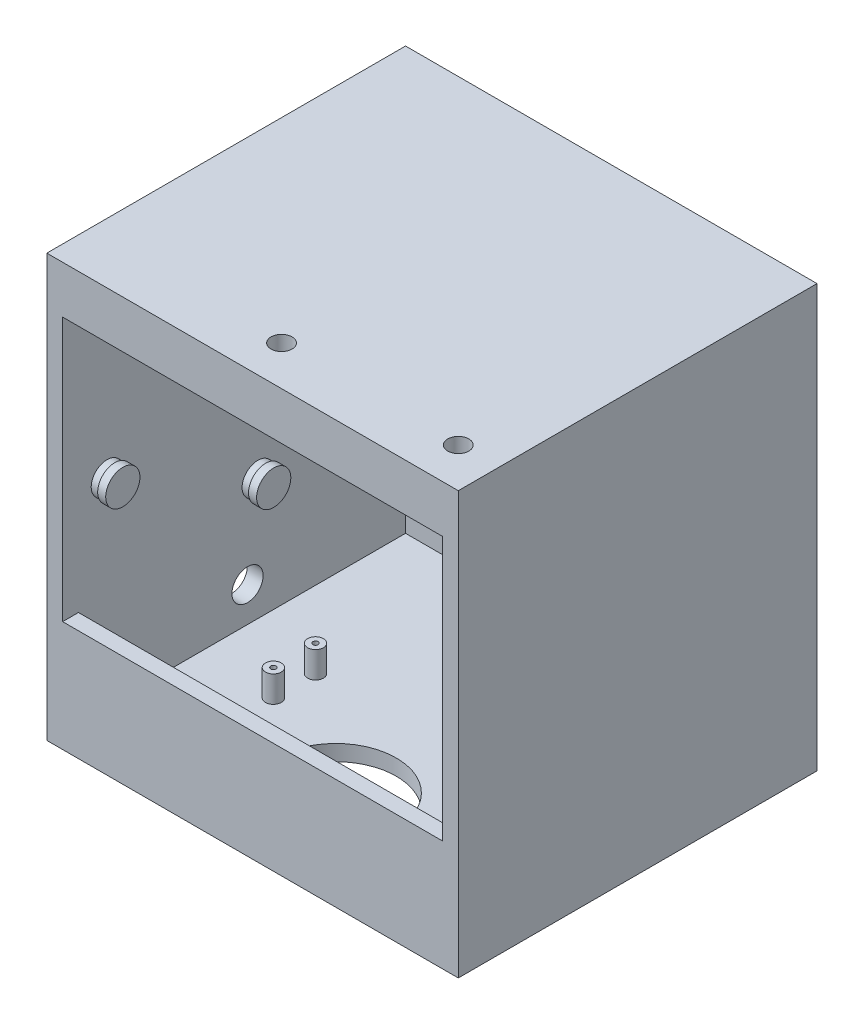
SolidWorks part; units mm, degrees
ref_plane "Front Plane" through (0, 0, 0) normal (0, 0, 1) x (1, 0, 0)
ref_plane "Top Plane" through (0, 0, 0) normal (0, 1, 0) x (1, 0, 0)
ref_plane "Right Plane" through (0, 0, 0) normal (1, 0, 0) x (0, 0, -1)
sketch "Base Plate Sketch" plane through (0, 0, 0) normal (0, 1, 0) x (1, 0, 0)
  line L1 (-176.9042, 232.645) -> (280.2958, 232.645)
  line L2 (-176.9042, 232.645) -> (-176.9042, -161.055)
  line L3 (-176.9042, -161.055) -> (280.2958, -161.055)
  line L4 (280.2958, 232.645) -> (280.2958, -161.055)
  line L5 (-195.9542, 251.695) -> (299.3458, 251.695)
  line L6 (-195.9542, 251.695) -> (-195.9542, -180.105)
  line L7 (-195.9542, -180.105) -> (299.3458, -180.105)
  line L8 (299.3458, 251.695) -> (299.3458, -180.105)
  line L9 (51.6958, 232.645) -> (51.6958, -161.055)
  circle A0 centre (51.6958, -80.0925) radius 73.025
  circle A1 centre (-72.1292, -82.0299) radius 4.1
  circle A2 centre (-72.1292, 203.67) radius 4.7625
  circle A3 centre (-84.8292, 32.22) radius 9.5
  circle A4 centre (-84.8292, -18.5299) radius 9.5
  circle A5 centre (-84.8292, 32.22) radius 3.175
  circle A6 centre (-84.8292, -18.5299) radius 3.175
  circle A7 centre (175.5208, -82.0299) radius 4.1
  circle A8 centre (188.2208, -18.5299) radius 3.175
  circle A9 centre (188.2208, -18.5299) radius 9.5
  circle A10 centre (188.2208, 32.22) radius 3.175
  circle A11 centre (188.2208, 32.22) radius 9.5
  circle A12 centre (175.5208, 203.67) radius 4.7625
  dimension "D7" = 146.05
  dimension "D9" = 8.2
  dimension "D10" = 12.7
  dimension "D11" = 63.5
  dimension "D12" = 9.525
  dimension "D13" = 12.7
  dimension "D14" = 19
  dimension "D15" = 19
  dimension "D19" = 6.35
  dimension "D20" = 6.35
  dimension "D1" = 393.7
  dimension "D2" = 457.2
  dimension "D3" = 19.05
  dimension "D4" = 19.05
  dimension "D5" = 19.05
  dimension "D6" = 19.05
  dimension "D8" = 312.7375
  dimension "D16" = 50.75
  dimension "D17" = 123.825
  dimension "D21" = 28.975
  dimension "D22" = 171.45
extrude "Boss-Extrude2" add sketch "Base Plate Sketch" along normal blind 31.75 contours A10 | A11 | A8 | A9 | A5 | A3 | A6 | A4
extrude "Boss-Extrude3" add sketch "Sketch1<5>" against normal blind 19.05 contours L5 L8 L7 L6
sketch "Sketch1<5>" plane through (0, 0, 0) normal (0, 1, 0) x (1, 0, 0) same geometry as "Base Plate Sketch"
extrude "Cut-Extrude1" cut sketch "Sketch1<6>" against normal blind 99.05 contours A2 | A1 | A0 | A7 | A12
sketch "Sketch1<6>" plane through (0, 0, 0) normal (0, 1, 0) x (1, 0, 0) same geometry as "Base Plate Sketch"
extrude "Boss-Extrude4" add sketch "Sketch1<7>" along normal blind 469.9 contours L6 L7 L8 L5 | L2 L3 L4 L1
sketch "Sketch1<7>" plane through (0, 0, 0) normal (0, 1, 0) x (1, 0, 0) same geometry as "Base Plate Sketch"
ref_plane "Plane1" through (-176.9042, 0, -232.645) normal (1, 0, 0) x (0, 0, -1)
sketch "Back Wall Sketch" plane through (0, 0, -232.645) normal (0, 0, 1) x (1, 0, 0)
  line L0 (-176.9042, 114.3) -> (280.2958, 114.3)
  line L1 (-176.9042, 469.9) -> (-176.9042, 0) construction
  line L2 (280.2958, 469.9) -> (280.2958, 0) construction
  line L3 (-176.9042, 266.7) -> (280.2958, 266.7)
  line L4 (-176.9042, 0) -> (280.2958, 0) construction
  line L5 (-176.9042, 469.9) -> (280.2958, 469.9) construction
  line L6 (51.6958, 266.7) -> (51.6958, 469.9)
  line L7 (280.2958, 266.7) -> (280.2958, 114.3)
  line L8 (-176.9042, 266.7) -> (-176.9042, 114.3)
  circle A0 centre (-117.9716, 342.325) radius 1.875
  circle A2 centre (-21.0417, 294.9875) radius 1.875
  circle A4 centre (-117.9716, 316.575) radius 1.875
  circle A5 centre (124.4333, 294.9875) radius 1.875
  circle A6 centre (221.3633, 342.325) radius 1.875
  circle A7 centre (221.3633, 316.575) radius 1.875
  circle A8 centre (184.1213, 148.3) radius 16.8
  dimension "D3" = 3.75
  dimension "D4" = 3.75
  dimension "D5" = 3.75
  dimension "D10" = 33.6
  dimension "D1" = 114.3
  dimension "D2" = 152.4
  dimension "D6" = 127.575
  dimension "D7" = 25.75
  dimension "D8" = 174.9125
  dimension "D9" = 155.8625
  dimension "D11" = 96.1746
  dimension "D12" = 118.4
extrude "Boss-Extrude5" add sketch "Back Wall Sketch" against normal blind 38.3 contours L8 L0 L7 L3
extrude "Cut-Extrude2" cut sketch "Back Wall Sketch<5>" against normal blind 19.25 contours L3 L7 L0 L8
sketch "Back Wall Sketch<5>" plane through (0, 0, -232.645) normal (0, 0, 1) x (1, 0, 0) same geometry as "Back Wall Sketch"
extrude "Cut-Extrude5" cut sketch "Back Wall Sketch<7>" against normal blind 28.875 contours A8
sketch "Back Wall Sketch<7>" plane through (0, 0, -232.645) normal (0, 0, 1) x (1, 0, 0) same geometry as "Back Wall Sketch"
extrude "Cut-Extrude6" cut sketch "Back Wall Sketch<8>" against normal blind 28.875 contours A2 | A4 | A0 | A6 | A7 | A5
sketch "Back Wall Sketch<8>" plane through (0, 0, -232.645) normal (0, 0, 1) x (1, 0, 0) same geometry as "Back Wall Sketch"
sketch "Left Wall Sketch" plane through (-176.9042, 0, 0) normal (1, 0, 0) x (0, 0, -1)
  line L0 (232.645, 0) -> (-161.055, 0) construction
  line L1 (251.695, 266.7) -> (251.695, 114.3) construction
  line L2 (232.645, 114.3) -> (232.645, 0) construction
  circle A0 centre (-126.7142, 237.44) radius 19
  circle A1 centre (54.8951, 146) radius 19
  circle A2 centre (42.445, 41.61) radius 18.75
  dimension "D1" = 38
  dimension "D2" = 38
  dimension "D3" = 37.5
  dimension "D5" = 146
  dimension "D9" = 41.61
  dimension "D4" = 237.44
  dimension "D6" = 378.4092
  dimension "D7" = 196.8
  dimension "D8" = 190.2
extrude "Cut-Extrude7" cut sketch "Left Wall Sketch" against normal blind 28.875 contours A2
extrude "Boss-Extrude6" add sketch "Left Wall Sketch<3>" along normal blind 9.35 contours A1 | A0
sketch "Left Wall Sketch<3>" plane through (-176.9042, 0, 0) normal (1, 0, 0) x (0, 0, -1) same geometry as "Left Wall Sketch"
sketch "Sketch5" plane through (-167.5542, 0, 0) normal (1, 0, 0) x (0, 0, -1)
  circle A0 centre (-126.7142, 237.44) radius 20.6
  circle A1 centre (54.8951, 146) radius 20.6
  dimension "D1" = 41.2
  dimension "D2" = 41.2
extrude "Boss-Extrude7" add sketch "Sketch5" along normal blind 9.7
sketch "Chamber Door Sketch" plane through (0, 0, 161.055) normal (0, 0, -1) x (-1, 0, 0)
  line L0 (-280.2958, 431.8) -> (176.9042, 431.8)
  line L1 (-280.2958, 469.9) -> (-280.2958, 0) construction
  line L2 (176.9042, 469.9) -> (176.9042, 0) construction
  line L3 (-280.2958, 114.3) -> (176.9042, 114.3)
  line L4 (176.9042, 0) -> (-280.2958, 0) construction
  line L5 (176.9042, 469.9) -> (-280.2958, 469.9) construction
  line L6 (-280.2958, 431.8) -> (-280.2958, 114.3)
  line L7 (176.9042, 431.8) -> (176.9042, 114.3)
  dimension "D1" = 114.3
  dimension "D2" = 38.1
extrude "Cut-Extrude8" cut sketch "Chamber Door Sketch" against normal blind 25.4 contours L0 L7 L3 L6
sketch "Top Sketch" plane through (0, 469.9, 0) normal (0, 1, 0) x (1, 0, 0)
  line L1 (-195.9542, 251.695) -> (299.3458, 251.695)
  line L2 (-195.9542, 251.695) -> (-195.9542, -180.105)
  line L3 (-195.9542, -180.105) -> (299.3458, -180.105)
  line L4 (299.3458, 251.695) -> (299.3458, -180.105)
extrude "Boss-Extrude8" add sketch "Top Sketch" along normal blind 19.05 contours L4 L3 L2 L1
sketch "Sketch7" plane through (0, 469.9, 0) normal (0, -1, 0) x (1, 0, 0)
  line L0 (-176.9042, -232.645) -> (280.2958, -232.645) construction
  line L1 (22.0201, -181.825) -> (11.0101, -162.755)
  line L2 (11.0101, -162.755) -> (-11.0101, -162.755)
  line L3 (-11.0101, -162.755) -> (-22.0201, -181.825)
  line L4 (-22.0201, -181.825) -> (-11.0101, -200.895)
  line L5 (-11.0101, -200.895) -> (11.0101, -200.895)
  line L6 (11.0101, -200.895) -> (22.0201, -181.825)
  circle A0 centre (0, -181.825) radius 19.07 construction
  point P1 (0, -200.895)
  dimension "D1" = 38.14
  dimension "D2" = 31.75
extrude "Boss-Extrude9" add sketch "Sketch7" along normal blind 12.7 contours L2 L3 L4 L5 L6 L1
sketch "Sketch8" plane through (0, 488.95, 0) normal (0, 1, 0) x (1, 0, 0)
  line L2 (-195.9542, -180.105) -> (299.3458, -180.105) construction
  line L3 (-195.9542, 251.695) -> (-195.9542, -180.105) construction
  line L4 (299.3458, 251.695) -> (299.3458, -180.105) construction
  circle A0 centre (38.9958, -132.48) radius 12.7
  circle A1 centre (251.7208, -132.48) radius 12.7
  dimension "D1" = 47.625
  dimension "D4" = 25.4
  dimension "D2" = 234.95
  dimension "D3" = 47.625
extrude "Cut-Extrude9" cut sketch "Sketch8" against normal up to next (19.05 mm away)
sketch "Sketch9" plane through (-176.9042, 0, 0) normal (1, 0, 0) x (0, 0, -1)
  line L0 (232.645, 114.3) -> (232.645, 0) construction
  line L1 (232.645, 0) -> (-161.055, 0) construction
  circle A0 centre (170.145, 102) radius 12.7
  dimension "D1" = 62.5
  dimension "D3" = 25.4
  dimension "D2" = 102
extrude "Cut-Extrude10" cut sketch "Sketch9" against normal up to next (19.05 mm away)
